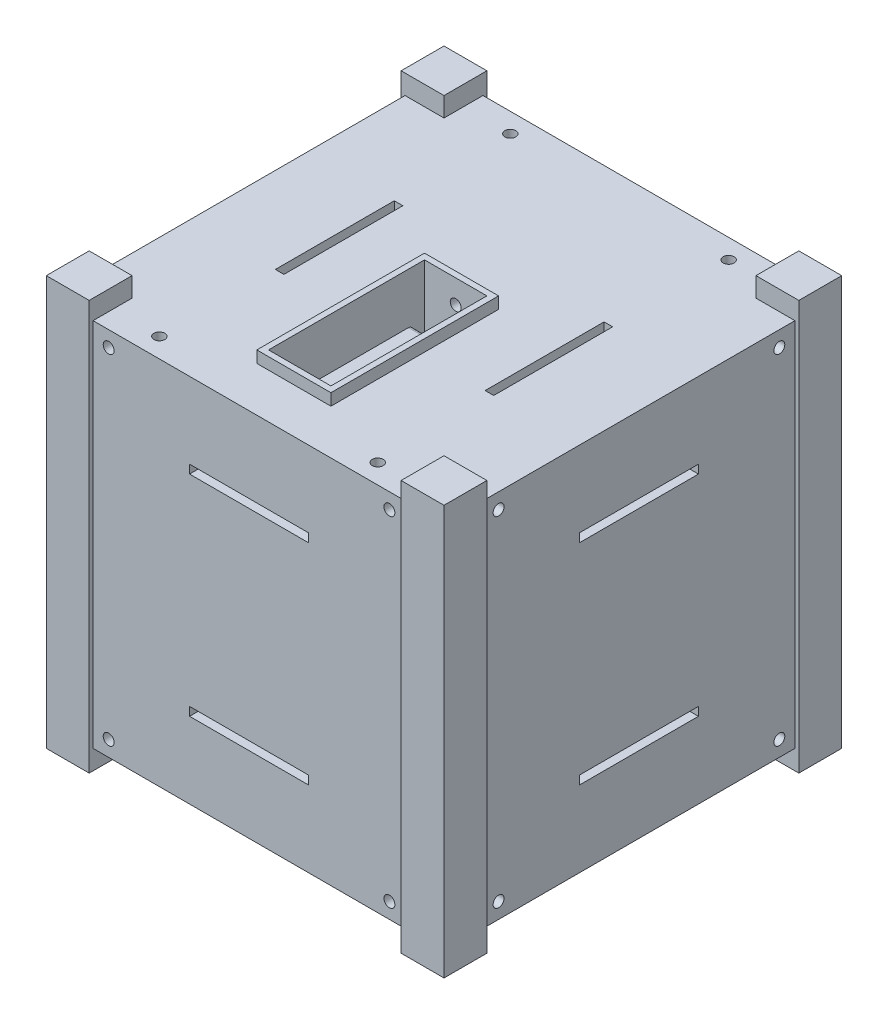
SolidWorks part; units mm, degrees
ref_plane "Front Plane" through (0, 0, 0) normal (0, 0, 1) x (1, 0, 0)
ref_plane "Top Plane" through (0, 0, 0) normal (0, 1, 0) x (1, 0, 0)
ref_plane "Right Plane" through (0, 0, 0) normal (1, 0, 0) x (0, 0, -1)
sketch "Sketch1" plane through (0, 0, 0) normal (0, 1, 0) x (1, 0, 0)
  line L1 (-50, 50) -> (50, 50)
  line L2 (-50, 50) -> (-50, -50)
  line L3 (-50, -50) -> (50, -50)
  line L4 (50, 50) -> (50, -50)
  line L5 (-50, 50) -> (50, -50) construction
  line L6 (-50, -50) -> (50, 50) construction
  point P0 (0, 0)
  dimension "D1" = 100
  dimension "D2" = 100
extrude "Boss-Extrude1" add sketch "Sketch1" along normal blind 95
ref_plane "Plane1" through (0, 100, 0) normal (0, 1, 0) x (1, 0, 0)
sketch "Sketch2" plane through (0, 100, 0) normal (0, 1, 0) x (1, 0, 0)
  line L0 (0, 0) -> (0, 71.0273) construction
  line L1 (-50, 50) -> (-40, 50)
  line L2 (-50, 50) -> (-50, 40)
  line L3 (-50, 40) -> (-40, 40)
  line L4 (-40, 50) -> (-40, 40)
  line L5 (50, 40) -> (40, 40)
  line L6 (40, 50) -> (40, 40)
  line L7 (50, 50) -> (40, 50)
  line L8 (50, 50) -> (50, 40)
  line L9 (0, 0) -> (-74.2097, 0) construction
  line L10 (50, -50) -> (50, -40)
  line L11 (50, -50) -> (40, -50)
  line L12 (40, -50) -> (40, -40)
  line L13 (50, -40) -> (40, -40)
  line L14 (-50, -40) -> (-40, -40)
  line L15 (-40, -50) -> (-40, -40)
  line L16 (-50, -50) -> (-40, -50)
  line L17 (-50, -50) -> (-50, -40)
  dimension "D1" = 10
  dimension "D2" = 10
extrude "Boss-Extrude2" add sketch "Sketch2" against normal blind 105
sketch "Sketch3" plane through (0, 95, 0) normal (0, 1, 0) x (1, 0, 0)
  line L0 (0, 0) -> (-55.4811, 0) construction
  line L1 (0, 0) -> (0, -56.887) construction
  line L3 (50, -40) -> (40, -40) construction
  circle A0 centre (-28, -45) radius 1.4
  circle A1 centre (28, -45) radius 1.4
  circle A2 centre (28, 45) radius 1.4
  circle A3 centre (-28, 45) radius 1.4
  dimension "D1" = 2.8
  dimension "D2" = 28
  dimension "D3" = 85
extrude "Cut-Extrude1" cut sketch "Sketch3" against normal blind 10
sketch "Sketch4" plane through (0, 100, 0) normal (0, 1, 0) x (1, 0, 0)
  line L0 (-50, 50) -> (-50, 40) construction
  line L1 (-40, 40) -> (-51, 40)
  line L2 (-40, 40) -> (-40, 51)
  line L3 (-40, 51) -> (-51, 51)
  line L4 (-51, 40) -> (-51, 51)
  line L5 (40, 50) -> (-40, 50) construction
  line L6 (0, 0) -> (0, 60.0537) construction
  line L7 (0, 0) -> (-61.4769, 0) construction
  line L8 (40, 51) -> (51, 51)
  line L9 (51, 40) -> (51, 51)
  line L10 (40, 40) -> (51, 40)
  line L11 (40, 40) -> (40, 51)
  line L12 (40, -40) -> (40, -51)
  line L13 (40, -40) -> (51, -40)
  line L14 (51, -40) -> (51, -51)
  line L15 (40, -51) -> (51, -51)
  line L16 (-40, -51) -> (-51, -51)
  line L17 (-51, -40) -> (-51, -51)
  line L18 (-40, -40) -> (-51, -40)
  line L19 (-40, -40) -> (-40, -51)
  dimension "D1" = 1
  dimension "D2" = 1
extrude "Boss-Extrude3" add sketch "Sketch4" against normal up to surface (105 mm away) up to face at (-45, -5, -45)
sketch "Sketch5" plane through (0, 0, 50) normal (0, 0, 1) x (1, 0, 0)
  line L0 (0, 95) -> (0, 43.7031) construction
  line L1 (-40, 95) -> (40, 95) construction
  line L2 (40, 47.5) -> (-59.8843, 47.5) construction
  line L3 (40, 0) -> (40, 95) construction
  line L4 (-40, 95) -> (-40, 0) construction
  circle A0 centre (-36, 91) radius 1.4
  circle A1 centre (36, 91) radius 1.4
  circle A2 centre (36, 4) radius 1.4
  circle A3 centre (-36, 4) radius 1.4
  dimension "D1" = 2.8
  dimension "D2" = 4
  dimension "D3" = 4
extrude "Cut-Extrude2" cut sketch "Sketch5" against normal blind 10
mirror "Mirror1" about plane through (0, 0, 0) normal (0, 0, 1) of "Cut-Extrude2"
sketch "Sketch6" plane through (-50, 0, 0) normal (-1, 0, 0) x (0, 0, 1)
  line L0 (-40, 95) -> (-40, 0) construction
  line L1 (-40, 95) -> (40, 95) construction
  line L2 (0, 95) -> (0, 40.4022) construction
  line L3 (-40, 47.5) -> (36.0105, 47.5) construction
  line L4 (-40, -5) -> (-40, 100) construction
  circle A0 centre (-36, 91) radius 1.4
  circle A1 centre (36, 91) radius 1.4
  circle A2 centre (36, 4) radius 1.4
  circle A3 centre (-36, 4) radius 1.4
  dimension "D1" = 2.8
  dimension "D2" = 4
  dimension "D3" = 4
extrude "Cut-Extrude3" cut sketch "Sketch6" against normal blind 10
mirror "Mirror2" about plane through (0, 0, 0) normal (1, 0, 0) of "Cut-Extrude3"
ref_plane "Plane2" through (0, 47.5, 0) normal (0, 1, 0) x (1, 0, 0)
mirror "Mirror3" about plane through (0, 47.5, 0) normal (0, 1, 0) of "Cut-Extrude1"
sketch "Sketch7" plane through (0, 95, 0) normal (0, 1, 0) x (1, 0, 0)
  line L0 (9.5, 4.5) -> (9.5, -38.5)
  line L1 (-8, 3) -> (8, 3)
  line L2 (-8, 3) -> (-8, -37)
  line L3 (-8, -37) -> (8, -37)
  line L4 (8, 3) -> (8, -37)
  line L5 (-9.5, -38.5) -> (9.5, -38.5)
  line L6 (-9.5, 4.5) -> (-9.5, -38.5)
  line L7 (-9.5, 4.5) -> (9.5, 4.5)
  dimension "D1" = 8
  dimension "D2" = 8
  dimension "D3" = 3
  dimension "D4" = 40
  dimension "D5" = 1.5
extrude "Boss-Extrude4" add sketch "Sketch7" along normal blind 3
sketch "Sketch8" plane through (0, 95, 0) normal (0, 1, 0) x (1, 0, 0)
  line L4 (-8, 3) -> (-8, -37)
  line L5 (-8, -37) -> (8, -37)
  line L6 (8, -37) -> (8, 3)
  line L7 (8, 3) -> (-8, 3)
  line L8 (-8, 3) -> (-8, -37)
  line L9 (-8, -37) -> (8, -37)
  line L10 (8, -37) -> (8, 3)
  line L11 (8, 3) -> (-8, 3)
  dimension "D1" = 0
extrude "Cut-Extrude4" cut sketch "Sketch8" against normal blind 10
chamfer "Chamfer2" distance 13 angle 45 1 edges at (0, 85, 37)
sketch "Sketch9" plane through (0, 85, 0) normal (0, 1, 0) x (1, 0, 0)
  line L0 (8, -24) -> (8, 3) construction
  line L1 (-8, 3) -> (8, 3)
  line L2 (-8, 3) -> (-8, -0.1)
  line L3 (-8, -0.1) -> (8, -0.1)
  line L4 (8, 3) -> (8, -0.1)
  dimension "D1" = 3.1
extrude "Cut-Extrude5" cut sketch "Sketch9" against normal blind 10
fillet "Fillet1" radius 1 1 edges at (0, 85, 0.1)
sketch "Sketch10" plane through (0, 0, -3) normal (0, 0, 1) x (1, 0, 0)
  line L0 (8, 98) -> (-8, 98) construction
  line L1 (-8, 98) -> (-8, 75) construction
  circle A0 centre (0, 92) radius 1.4
  dimension "D1" = 2.8
  dimension "D2" = 6
  dimension "D3" = 8
extrude "Cut-Extrude6" cut sketch "Sketch10" against normal blind 10
sketch "Sketch11" plane through (0, 0, 0) normal (0, -1, 0) x (1, 0, 0)
  line L0 (-50, -40) -> (-50, 40) construction
  circle A0 centre (0, -15) radius 5
  dimension "D1" = 10
  dimension "D2" = 15
  dimension "D3" = 50
extrude "Boss-Extrude5" add sketch "Sketch11" along normal blind 3
sketch "Sketch12" plane through (-50, 0, 0) normal (-1, 0, 0) x (0, 0, 1)
  line L0 (-40, 95) -> (40, 95) construction
  line L1 (-15.25, 75.5) -> (15.25, 75.5)
  line L2 (-15.25, 75.5) -> (-15.25, 73.3)
  line L3 (-15.25, 73.3) -> (15.25, 73.3)
  line L4 (15.25, 75.5) -> (15.25, 73.3)
  line L5 (-15.25, 75.5) -> (15.25, 73.3) construction
  line L6 (-15.25, 73.3) -> (15.25, 75.5) construction
  line L7 (0, 95) -> (0, 60.126) construction
  line L8 (-51, 47.5) -> (62.2361, 47.5) construction
  line L9 (-51, -5) -> (-51, 100) construction
  line L10 (-15.25, 21.7) -> (15.25, 21.7)
  line L11 (15.25, 19.5) -> (15.25, 21.7)
  line L12 (-15.25, 19.5) -> (15.25, 19.5)
  line L13 (-15.25, 19.5) -> (-15.25, 21.7)
  point P0 (0, 74.4)
  dimension "D1" = 19.5
  dimension "D2" = 2.2
  dimension "D3" = 30.5
extrude "Cut-Extrude7" cut sketch "Sketch12" against normal blind 3
mirror "Mirror4" about plane through (0, 0, 0) normal (1, 0, 0) of "Cut-Extrude7"
sketch "Sketch13" plane through (0, 0, 50) normal (0, 0, 1) x (1, 0, 0)
  line L0 (0, 95) -> (0, 46.2553) construction
  line L1 (-40, 95) -> (40, 95) construction
  line L2 (-51, 47.5) -> (61.8656, 47.5) construction
  line L3 (-15.25, 75.5) -> (15.25, 75.5)
  line L4 (-15.25, 75.5) -> (-15.25, 73.3)
  line L5 (-15.25, 73.3) -> (15.25, 73.3)
  line L6 (15.25, 75.5) -> (15.25, 73.3)
  line L7 (-15.25, 75.5) -> (15.25, 73.3) construction
  line L8 (-15.25, 73.3) -> (15.25, 75.5) construction
  line L9 (-51, -5) -> (-51, 100) construction
  line L10 (-15.25, 21.7) -> (15.25, 21.7)
  line L11 (15.25, 19.5) -> (15.25, 21.7)
  line L12 (-15.25, 19.5) -> (15.25, 19.5)
  line L13 (-15.25, 19.5) -> (-15.25, 21.7)
  point P5 (0, 74.4)
  dimension "D1" = 30.5
  dimension "D2" = 2.2
  dimension "D3" = 19.5
extrude "Cut-Extrude8" cut sketch "Sketch13" against normal blind 3
mirror "Mirror5" about plane through (0, 0, 0) normal (0, 0, 1) of "Cut-Extrude8"
sketch "Sketch14" plane through (0, 95, 0) normal (0, 1, 0) x (1, 0, 0)
  line L0 (-50, 0) -> (73.3052, 0) construction
  line L1 (-50, 40) -> (-50, -40) construction
  line L2 (0, 50) -> (0, -6.1969) construction
  line L3 (40, 50) -> (-40, 50) construction
  line L4 (28, 15.25) -> (25.8, 15.25)
  line L5 (-28, -15.25) -> (-25.8, -15.25)
  line L6 (-28, -15.25) -> (-28, 15.25)
  line L7 (-28, 15.25) -> (-25.8, 15.25)
  line L8 (-25.8, -15.25) -> (-25.8, 15.25)
  line L9 (-28, -15.25) -> (-25.8, 15.25) construction
  line L10 (-28, 15.25) -> (-25.8, -15.25) construction
  line L11 (25.8, -15.25) -> (25.8, 15.25)
  line L12 (28, -15.25) -> (25.8, -15.25)
  line L13 (28, -15.25) -> (28, 15.25)
  point P9 (-26.9, 0)
  dimension "D1" = 30.5
  dimension "D2" = 2.2
  dimension "D3" = 22
extrude "Cut-Extrude9" cut sketch "Sketch14" against normal blind 3
mirror "Mirror6" about plane through (0, 47.5, 0) normal (0, 1, 0) of "Cut-Extrude9"
sketch "Sketch19" plane through (0, 100, 0) normal (0, 1, 0) x (1, 0, 0)
  line L1 (-51, 51) -> (-40, 51)
  line L2 (-51, 51) -> (-51, 40)
  line L3 (-51, 40) -> (-40, 40)
  line L4 (-40, 51) -> (-40, 40)
  line L5 (40, 51) -> (51, 51)
  line L6 (40, 51) -> (40, 40)
  line L7 (40, 40) -> (51, 40)
  line L8 (51, 51) -> (51, 40)
